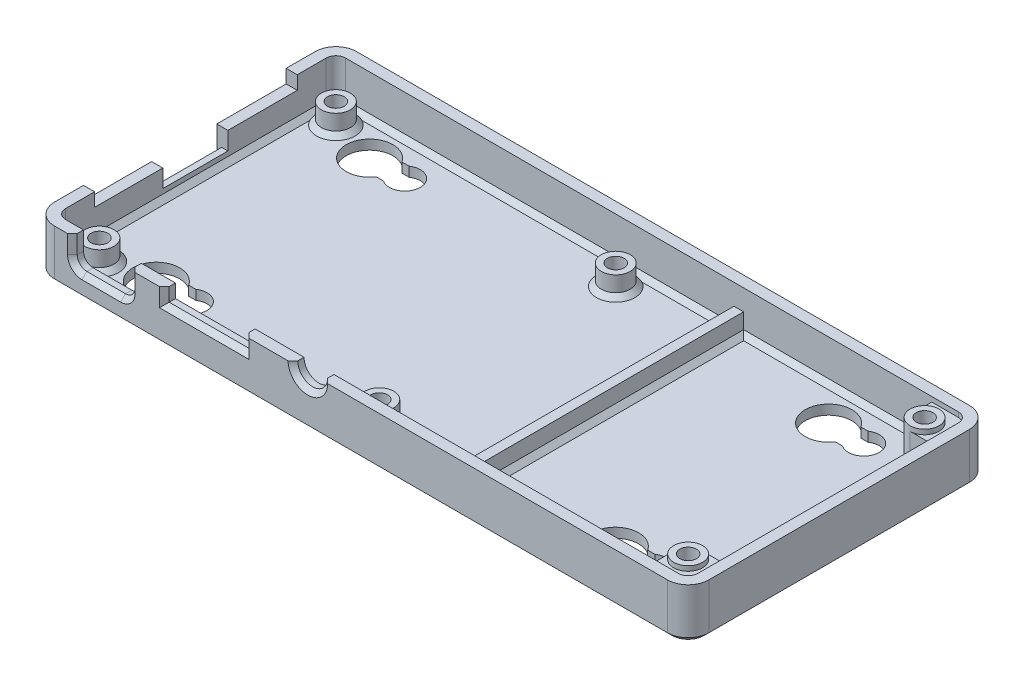
SolidWorks part; units mm, degrees
ref_plane "Front Plane" through (0, 0, 0) normal (0, 0, 1) x (1, 0, 0)
ref_plane "Top Plane" through (0, 0, 0) normal (0, 1, 0) x (1, 0, 0)
ref_plane "Right Plane" through (0, 0, 0) normal (1, 0, 0) x (0, 0, -1)
sketch "Sketch1" plane through (0, 0, 0) normal (0, 1, 0) x (1, 0, 0)
  line L0 (-71.5618, 3.106) -> (57.4382, 3.106) construction
  line L1 (-71.5618, 31.106) -> (57.4382, 31.106)
  line L2 (-71.5618, 31.106) -> (-71.5618, -24.894)
  line L3 (-71.5618, -24.894) -> (57.4382, -24.894)
  line L4 (57.4382, 31.106) -> (57.4382, -24.894)
  line L5 (-60.6618, -24.894) -> (-60.6618, -31.6828) construction
  line L6 (-68.0618, 27.606) -> (-10.0618, 27.606)
  line L7 (-68.0618, 27.606) -> (-68.0618, -21.394)
  line L8 (-68.0618, -21.394) -> (-10.0618, -21.394)
  line L9 (-10.0618, 27.606) -> (-10.0618, -21.394)
  line L10 (-39.5618, -24.894) -> (-39.5618, -31.6828) construction
  line L11 (-18.0618, -24.894) -> (-18.0618, -31.6828) construction
  line L12 (-65.4118, -26.5648) -> (-55.9118, -26.5648) construction
  line L13 (-48.0618, -26.5648) -> (-31.0618, -26.5648) construction
  line L14 (-22.0618, -26.5648) -> (-14.0618, -26.5648) construction
  line L15 (-72.5618, 9.606) -> (-72.5618, -3.394) construction
  line L16 (-71.5618, 3.106) -> (-72.5618, 3.106) construction
  dimension "D1" = 129
  dimension "D2" = 56
  dimension "D3" = 49
  dimension "D4" = 58
  dimension "D5" = 3.5
  dimension "D6" = 3.5
  dimension "D7" = 10.9
  dimension "D8" = 32
  dimension "D9" = 53.5
  dimension "D10" = 2
  dimension "D11" = 13
  dimension "D12" = 9.5
  dimension "D13" = 17
  dimension "D14" = 8
sketch "Sketch3" plane through (0, 0, 0) normal (0, 1, 0) x (1, 0, 0)
  line L4 (60.7382, 34.406) -> (-74.8618, 34.406)
  line L5 (-74.8618, 34.406) -> (-74.8618, -28.194)
  line L6 (-74.8618, -28.194) -> (60.7382, -28.194)
  line L7 (60.7382, -28.194) -> (60.7382, 34.406)
  line L8 (58.4382, 32.106) -> (-72.5618, 32.106)
  line L9 (58.4382, -25.894) -> (58.4382, 32.106)
  line L10 (-72.5618, -25.894) -> (58.4382, -25.894)
  line L11 (-72.5618, 32.106) -> (-72.5618, -25.894)
  line L12 (58.4382, 32.106) -> (-72.5618, 32.106)
  line L13 (58.4382, -25.894) -> (58.4382, 32.106)
  line L14 (-72.5618, -25.894) -> (58.4382, -25.894)
  line L15 (-72.5618, 32.106) -> (-72.5618, -25.894)
  line L16 (-7.0618, 3.106) -> (-7.0618, 34.406) construction
  line L17 (-71.5618, 3.106) -> (57.4382, 3.106) construction
  line L20 (-74.8618, 3.106) -> (52.7382, 3.106) construction
  line L25 (60.7382, -28.194) -> (60.7382, 34.406) construction
  line L26 (58.4382, -25.894) -> (58.4382, 32.106) construction
  dimension "D1" = 1
  dimension "D2" = 2.3
extrude "Boss-Extrude1" add sketch "Sketch3" along normal blind 10.5
sketch "Sketch5" plane through (0, 0, 0) normal (0, 1, 0) x (1, 0, 0)
  line L1 (-72.5618, 32.106) -> (58.4382, 32.106)
  line L2 (-72.5618, 32.106) -> (-72.5618, -25.894)
  line L3 (-72.5618, -25.894) -> (58.4382, -25.894)
  line L4 (58.4382, 32.106) -> (58.4382, -25.894)
extrude "Boss-Extrude2" add sketch "Sketch5" along normal blind 2
sketch "Sketch6" plane through (0, 2, 0) normal (0, 1, 0) x (1, 0, 0)
  circle A0 centre (-68.0618, 27.606) radius 3
  circle A1 centre (-68.0618, -21.394) radius 3
  circle A2 centre (-10.0618, -21.394) radius 3
  circle A3 centre (-10.0618, 27.606) radius 3
extrude "Boss-Extrude3" add sketch "Sketch6" along normal blind 4.2
sketch "Sketch10" plane through (0, 2, 0) normal (0, 1, 0) x (1, 0, 0)
  line L0 (58.4382, 32.106) -> (-72.5618, 32.106) construction
  line L1 (9.9382, 32.106) -> (11.9382, 32.106)
  line L2 (9.9382, 32.106) -> (9.9382, -25.894)
  line L3 (9.9382, -25.894) -> (11.9382, -25.894)
  line L4 (11.9382, 32.106) -> (11.9382, -25.894)
  line L5 (-72.5618, -25.894) -> (58.4382, -25.894) construction
  line L6 (-10.0618, 27.606) -> (-10.0618, -21.394) construction
  dimension "D1" = 2
  dimension "D2" = 20
extrude "Boss-Extrude4" add sketch "Sketch10" along normal blind 4.2
sketch "Sketch11" plane through (0, 0, 28.194) normal (0, 0, 1) x (1, 0, 0)
  line L0 (-74.8618, 10.5) -> (-74.8618, 0) construction
  line L1 (-66.8618, 10.5) -> (-54.8618, 10.5)
  line L2 (-66.8618, 10.5) -> (-66.8618, 4.7)
  line L3 (-66.8618, 4.7) -> (-54.8618, 4.7)
  line L4 (-54.8618, 10.5) -> (-54.8618, 4.7)
  line L6 (-60.8618, 10.5) -> (-60.6618, 0) construction
  line L7 (-65.4118, 0) -> (-55.9118, 0) construction
  line L9 (-47.8118, 10.5) -> (-31.3118, 10.5)
  line L10 (-47.8118, 10.5) -> (-47.8118, 7.7)
  line L11 (-47.8118, 7.7) -> (-31.3118, 7.7)
  line L12 (-31.3118, 10.5) -> (-31.3118, 7.7)
  line L14 (-39.5618, 0) -> (-39.5618, 10.5) construction
  line L15 (-48.0618, 0) -> (-31.0618, 0) construction
  line L16 (-18.0618, 0) -> (-18.0618, 10.5) construction
  line L17 (-22.0618, 0) -> (-14.0618, 0) construction
  line L18 (-74.8618, 10.5) -> (60.7382, 10.5) construction
  circle A0 centre (-18.0618, 10.5) radius 3.1
  point P6 (-39.5618, 10.5)
  point P7 (-60.6618, 11.3405)
  point P16 (-60.8618, 10.5)
  dimension "D5" = 6.2
  dimension "D2" = 12
  dimension "D4" = 16.5
  dimension "D6" = 8
  dimension "D7" = 5.8
  dimension "D8" = 2.8
extrude "Cut-Extrude1" cut sketch "Sketch11" against normal up to next
sketch "Sketch12" plane through (-74.8618, 0, 0) normal (-1, 0, 0) x (0, 0, 1)
  line L0 (-3.106, 0) -> (-3.106, 10.5) construction
  line L1 (-27.606, 0) -> (21.394, 0) construction
  line L2 (-34.406, 10.5) -> (28.194, 10.5) construction
  line L3 (-24.106, 7.7) -> (17.894, 7.7)
  line L4 (-9.7329, 7.7) -> (3.7671, 7.7)
  line L5 (-9.7329, 7.7) -> (-9.7329, 4)
  line L6 (-9.7329, 4) -> (3.7671, 4)
  line L7 (3.7671, 7.7) -> (3.7671, 4)
  line L8 (-24.106, 10.5) -> (17.894, 10.5)
  line L9 (-24.106, 10.5) -> (-24.106, 7.7)
  line L11 (17.894, 10.5) -> (17.894, 7.7)
  line L12 (-9.7329, 5.85) -> (3.7671, 5.85) construction
  point P17 (-3.106, 7.7)
  dimension "D1" = 13.5
  dimension "D2" = 2.8
  dimension "D3" = 3.7
  dimension "D4" = 6.5
extrude "Cut-Extrude2" cut sketch "Sketch12" against normal up to next contours L9 L3 L11 L8 | L7 L6 L5 L4
fillet "Fillet6" radius 2 1 edges at (58.4382, 6.25, -32.106)
fillet "Fillet8" radius 2 2 edges at (-72.5618, 6.25, 25.894) (-72.5618, 6.25, -32.106)
chamfer "Chamfer1" distance 1 angle 45 4 edges at (-68.0618, 2, 24.394) (-10.0618, 2, 24.394) (-10.0618, 2, -24.606) (-68.0618, 2, -24.606)
sketch "Sketch24" plane through (0, 2, 0) normal (0, 1, 0) x (1, 0, 0)
  line L0 (11.9382, 3.106) -> (61.5789, 3.106) construction
  line L1 (11.9382, -25.894) -> (11.9382, 32.106) construction
  line L2 (53.9382, -18.394) -> (58.4382, -18.394)
  line L3 (58.4382, -25.894) -> (58.4382, 30.106) construction
  line L4 (-68.0618, 27.606) -> (-10.0618, 27.606) construction
  line L5 (-68.0618, 27.606) -> (-68.0618, -21.394) construction
  line L6 (-68.0618, -21.394) -> (-10.0618, -21.394) construction
  line L7 (-10.0618, 27.606) -> (-10.0618, -21.394) construction
  line L8 (-10.0618, 27.606) -> (53.9382, 27.606) construction
  line L9 (-10.0618, 27.606) -> (-10.0618, -21.394) construction
  line L10 (-10.0618, -21.394) -> (53.9382, -21.394) construction
  line L11 (53.9382, 27.606) -> (53.9382, -21.394) construction
  line L12 (50.9382, -21.394) -> (50.9382, -25.894)
  line L13 (11.9382, -25.894) -> (58.4382, -25.894) construction
  line L14 (58.4382, -25.894) -> (58.4382, 30.106) construction
  line L15 (58.4382, -18.394) -> (58.4382, -25.894)
  line L16 (58.4382, -25.894) -> (50.9382, -25.894)
  line L17 (50.9382, 27.606) -> (50.9382, 32.106)
  line L18 (56.4382, 32.106) -> (-70.5618, 32.106) construction
  line L19 (53.9382, 24.606) -> (58.4382, 24.606)
  line L20 (58.4382, 24.606) -> (58.4382, 32.106)
  line L21 (58.4382, 32.106) -> (50.9382, 32.106)
  arc A0 (50.9382, -21.394) -> (53.9382, -18.394) centre (53.9382, -21.394) cw
  arc A1 (50.9382, 27.606) -> (53.9382, 24.606) centre (53.9382, 27.606) ccw
  dimension "D2" = 4.5
extrude "Boss-Extrude7" add sketch "Sketch24" along normal up to surface (8.5 mm away) up to face at (-8.3784, 10.5, -11.175)
fillet "Fillet20" radius 4.3 4 edges at (60.7382, 5.25, 28.194) (-74.8618, 5.25, -34.406) (-74.8618, 5.25, 28.194) (60.7382, 5.25, -34.406)
chamfer "Chamfer5" distance 1 angle 45 16 edges at (-71.976, 2, 25.3082) (-71.976, 2, -31.5202) (-30.3118, 2, 25.894) (-30.3118, 2, -32.106) (9.9382, 2, -3.106) (11.9382, 2, -3.106) (31.4382, 2, -32.106) (31.4382, 2, 25.894) (51.8169, 2, 19.2727) (58.4382, 2, -3.106) (51.8169, 2, -25.4847) (-72.5618, 2, -3.106) (50.9382, 2, -29.856) (56.1882, 2, -24.606) (56.1882, 2, 18.394) (50.9382, 2, 23.644)
hole_wizard "CSK for #4 Flat Head Socket Cap Screw1" positions "Sketch28" profile "Sketch27" countersink size "#4" standard "ANSI Inch"
sketch "Sketch28" plane through (0, 0, 0) normal (0, -1, 0) x (-1, 0, 0)
  point P0 (68.0618, 27.606)
  point P4 (68.0618, -21.394)
  point P8 (-53.9382, 27.606)
  point P12 (-53.9382, -21.394)
  point P15 (10.0618, -21.394)
  point P19 (10.0618, 27.606)
sketch "Sketch27" plane through (-68.0618, 0, -27.606) normal (1, 0, 0) x (0, 0, -1)
  line L0 (0, 0) -> (0, 15.0378)
  line L1 (0, 15.0378) -> (1.7272, 14)
  line L2 (1.7272, 14) -> (1.7272, 1.8805)
  line L3 (1.7272, 1.8805) -> (3.3619, 0)
  line L5 (3.3619, 0) -> (0, 0)
  line L6 (-1.7272, 1.8805) -> (-3.3619, 0) construction
  line L10 (0, 15.0378) -> (-1.7272, 14) construction
  line L11 (0, -6.35) -> (0, 107.95) construction
  dimension "Hole Dia." = 3.4544
  dimension "Hole Depth" = 14
  dimension "Near C'Sink Dia." = 6.7238
  dimension "Near C'Sink Angle" = 82
  dimension "Drill Angle" = 118
chamfer "Chamfer7" distance 1 angle 45 8 edges at (-74.8618, 0, -3.106) (-73.6023, 0, 26.9346) (-73.6023, 0, -33.1466) (-7.0618, 0, 28.194) (-7.0618, 0, -34.406) (59.4788, 0, 26.9346) (59.4788, 0, -33.1466) (60.7382, 0, -3.106)
sketch "Sketch29" plane through (0, 10.5, 0) normal (0, 1, 0) x (1, 0, 0)
  line L0 (53.9382, 24.606) -> (58.4382, 24.606)
  line L1 (58.4382, 24.606) -> (58.4382, 30.106)
  line L2 (56.4382, 32.106) -> (50.9382, 32.106)
  line L3 (50.9382, 32.106) -> (50.9382, 27.606)
  line L4 (53.9382, -18.394) -> (58.4382, -18.394)
  line L5 (58.4382, -18.394) -> (58.4382, -23.894)
  line L6 (56.4382, -25.894) -> (50.9382, -25.894)
  line L7 (50.9382, -25.894) -> (50.9382, -21.394)
  arc A0 (53.9382, 24.606) -> (50.9382, 27.606) centre (53.9382, 27.606) ccw
  arc A1 (56.4382, 32.106) -> (58.4382, 30.106) centre (56.4382, 30.106) cw
  arc A2 (50.9382, -21.394) -> (53.9382, -18.394) centre (53.9382, -21.394) ccw
  arc A3 (56.4382, -25.894) -> (58.4382, -23.894) centre (56.4382, -23.894) ccw
extrude "Cut-Extrude3" cut sketch "Sketch29" against normal blind 1
fillet "Fillet21" radius 2 2 edges at (-54.8618, 4.7, 27.044) (-66.8618, 4.7, 27.044)
chamfer "Chamfer9" distance 1 angle 45 9 edges at (-18.0618, 7.4, 28.194) (-31.3118, 9.1, 28.194) (-39.5618, 7.7, 28.194) (-47.8118, 9.1, 28.194) (-54.8618, 8.6, 28.194) (-55.4476, 5.2858, 28.194) (-60.8618, 4.7, 28.194) (-66.276, 5.2858, 28.194) (-66.8618, 8.6, 28.194)
chamfer "Chamfer10" distance 1 angle 45 1 edges at (-74.8618, 4, -2.9829)
sketch "Sketch30" plane through (0, 2, 0) normal (0, 1, 0) x (1, 0, 0)
  line L0 (42.0442, 27.7882) -> (40.5638, 27.7882)
  line L1 (42.0442, 22.4728) -> (40.5638, 22.4728)
  line L2 (42.9186, 25.1305) -> (35.6093, 25.1305)
  line L3 (42.0442, -21.7208) -> (40.5638, -21.7208)
  line L4 (42.9186, -19.0631) -> (35.6093, -19.0631)
  line L5 (42.0442, -16.4054) -> (40.5638, -16.4054)
  line L6 (-53.0746, -21.7208) -> (-54.5549, -21.7208)
  line L7 (-53.0746, -16.4054) -> (-54.5549, -16.4054)
  line L8 (-53.0746, 22.4728) -> (-54.5549, 22.4728)
  line L9 (-53.0746, 27.7882) -> (-54.5549, 27.7882)
  line L10 (-52.2002, 25.1305) -> (-59.5094, 25.1305)
  line L11 (-52.2002, -19.0631) -> (-59.5094, -19.0631)
  arc A0 (40.5638, 27.7882) -> (40.5638, 22.4728) centre (36.5173, 25.1305) ccw
  arc A1 (42.0442, 22.4728) -> (42.0442, 27.7882) centre (43.8265, 25.1305) ccw
  arc A2 (40.5638, -16.4054) -> (40.5638, -21.7208) centre (36.5173, -19.0631) ccw
  arc A3 (42.0442, -21.7208) -> (42.0442, -16.4054) centre (43.8265, -19.0631) ccw
  arc A4 (-54.5549, -16.4054) -> (-54.5549, -21.7208) centre (-58.6015, -19.0631) ccw
  arc A5 (-54.5549, 27.7882) -> (-54.5549, 22.4728) centre (-58.6015, 25.1305) ccw
  arc A6 (-53.0746, 22.4728) -> (-53.0746, 27.7882) centre (-51.2922, 25.1305) ccw
  arc A7 (-53.0746, -21.7208) -> (-53.0746, -16.4054) centre (-51.2922, -19.0631) ccw
extrude "Cut-Extrude4" cut sketch "Sketch30" against normal through all contours L8 A6 L9 A5 | L6 A7 L7 A4 | L3 A3 L5 A2 | L1 A1 L0 A0 region at (46.845, 2, -25.1305) region at (41.304, 2, 21.5393) region at (-53.8147, 2, 21.5393) region at (-53.8147, 2, -22.6543)
